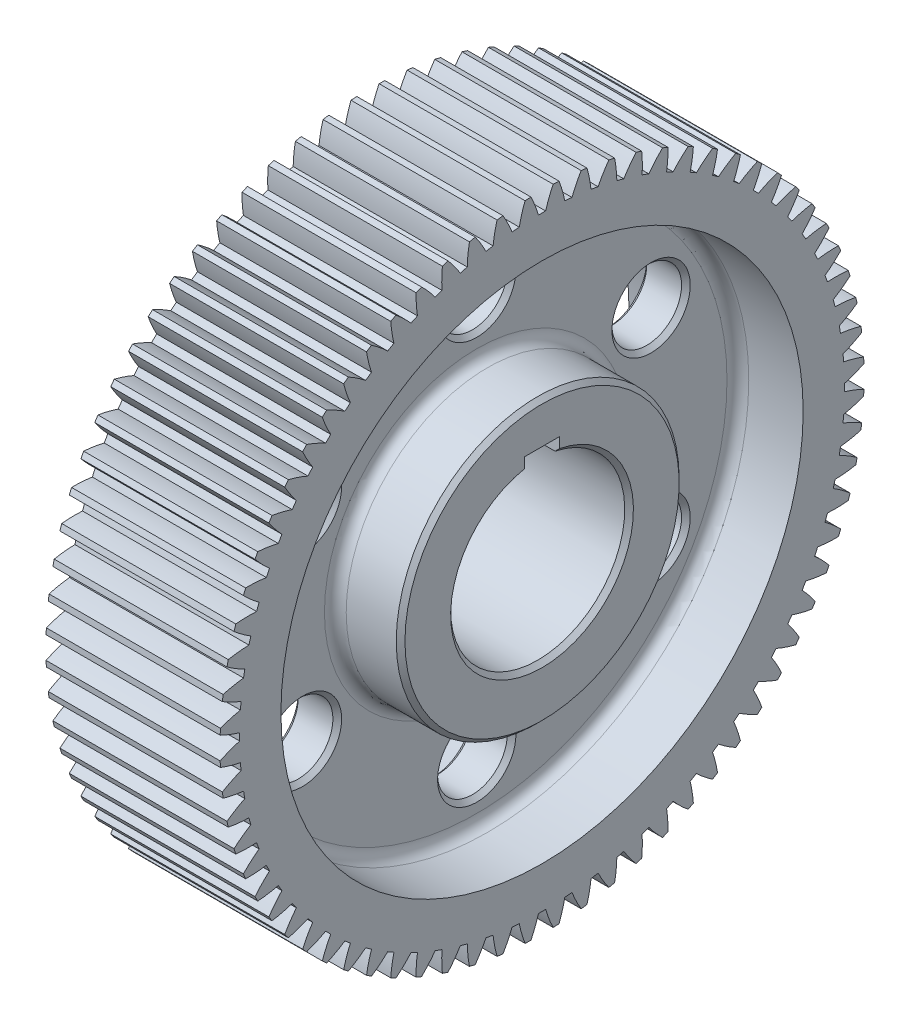
SolidWorks part; units mm, degrees
material "Plain Carbon Steel"
ref_plane "Plane1" through (0, 0, 0) normal (0, 0, 1) x (1, 0, 0)
ref_plane "Plane2" through (0, 0, 0) normal (0, 1, 0) x (1, 0, 0)
ref_plane "Plane3" through (0, 0, 0) normal (1, 0, 0) x (0, 0, -1)
sketch "HoldingSke" plane through (0, 0, 0) normal (0, 1, 0) x (1, 0, 0)
  line L0 (0, 0) -> (0.0773, -0.2378)
  line L1 (-15, 0) -> (100, 0) construction
  line L2 (0, 0) -> (-2.1039, 2.3779)
  line L3 (0, 0) -> (-11.863, 4.5341)
  line L4 (0, 0) -> (2.6687, 8.2133)
  line L5 (0, 0) -> (-46.8476, -17.4728)
  line L6 (0, 0) -> (-66.317, -44.7443)
  line L7 (-2.1039, 2.3779) -> (15.1161, 80.5027)
  line L8 (-76.2, 54.61) -> (-70.8, 54.61)
  line L9 (-71.009, 38.7566) -> (-53.1078, 45.2721)
  line L10 (-76.2, 71.12) -> (104.1128, 71.12)
  line L11 (0, 0) -> (-80, 0)
  line L12 (-76.2, 101.6) -> (-76.073, 101.6)
  line L13 (24.9733, 27.94) -> (52.9518, 28.4284)
  line L14 (24.9733, 27.94) -> (24.9743, 27.94)
  line L15 (24.9733, 27.94) -> (100.4006, 29.5858)
  line L16 (-63.627, -4) -> (-12.827, -4)
  circle A0 centre (0, 0) radius 40
  circle A1 centre (0, 0) radius 37.5
  circle A2 centre (0, 0) radius 37.5
  circle A3 centre (0, 0) radius 40
  dimension "Num_teeth" = 72
  dimension "Pitch_radius" = 180.3128
  dimension "Width" = 80
  dimension "Thickness" = 80
sketch "BasProSke" plane through (0, 0, 0) normal (0, 1, 0) x (1, 0, 0)
  line L0 (-10, 0) -> (60, 0) construction
  line L1 (0, 0) -> (0, 148)
  line L2 (0, 0) -> (80, 0)
  line L3 (80, 0) -> (80, 148)
  line L4 (80, 148) -> (0, 148)
  dimension "Thickness" = 80
  dimension "Diameter" = 296
revolve "Base-Revolve" add sketch "BasProSke" angle 360 about L0
sketch "TooCutSke" plane through (0, 0, 0) normal (1, 0, 0) x (0, 0, -1)
  line L1 (0, 0) -> (0, 107) construction
  line L2 (0, 0) -> (-3.3636, 143.9607) construction
  line L3 (0, 0) -> (-12.5598, 287.6668) construction
  line L4 (-3.3636, 143.9607) -> (-6.2799, 143.8334) construction
  arc A0 (1.6538, 138.9892) -> (-1.6538, 138.9892) centre (0, 0) ccw
  arc A1 (5.1137, 147.937) -> (-5.1137, 147.937) centre (0, 0) ccw
  circle A2 centre (0, 0) radius 144 construction
  circle A3 centre (0, 0) radius 135.3157 construction
  arc A4 (-1.6538, 138.9892) -> (-5.1137, 147.937) centre (-56.9206, 122.7615) ccw
  arc A5 (5.1137, 147.937) -> (1.6538, 138.9892) centre (56.9206, 122.7615) ccw
extrude "ToothCut" cut sketch "TooCutSke" along normal through all
fillet "Breaks" [suppressed] radius 0.08 tangent propagation no
fillet "RootFillets" [suppressed] radius 1.001
pattern_circular "TeethCuts" count 72 every 5 about axis through (-10, 0, 0) along (1, 0, 0) of "ToothCut", "RootFillets", "Breaks"
sketch "HubNeaOneSke" plane through (0, 0, 0) normal (-1, 0, 0) x (0, 0, 1)
  circle A0 centre (0, 0) radius 37.5
  dimension "Diameter" = 75
extrude "HubNearOne" [suppressed] add sketch "HubNeaOneSke" along normal blind 38.0001
sketch "HubNeaBotSke" plane through (0, 0, 0) normal (-1, 0, 0) x (0, 0, 1)
  circle A0 centre (0, 0) radius 37.5
  dimension "Diameter" = 75
extrude "HubNearBoth" [suppressed] add sketch "HubNeaBotSke" along normal blind 19
ref_plane "FarPln" through (80, 0, 0) normal (1, 0, 0) x (0, 0, -1)
sketch "HubFarSke" plane through (80, 0, 0) normal (1, 0, 0) x (0, 0, -1)
  circle A0 centre (0, 0) radius 37.5
  dimension "Diameter" = 75
extrude "HubFar" [suppressed] add sketch "HubFarSke" along normal blind 19
sketch "BorSke" plane through (0, 0, 0) normal (1, 0, 0) x (0, 0, -1)
  circle A0 centre (0, 0) radius 40
  dimension "Diameter" = 80
extrude "Bore" cut sketch "BorSke" along normal mid plane 160.0001
sketch "KeySke" plane through (0, 0, 0) normal (1, 0, 0) x (0, 0, -1)
  line L0 (-11, 0) -> (-11, 45.4)
  line L1 (-11, 45.4) -> (11, 45.4)
  line L2 (11, 45.4) -> (11, 0)
  line L3 (0, 0) -> (0, 34) construction
  line L4 (-11, 0) -> (11, 0)
  dimension "Width" = 22
extrude "Keyway" [suppressed] cut sketch "KeySke" along normal mid plane 160.0001
pattern_circular "Keyway2" [suppressed] count 2 every 90 about axis through (-10, 0, 0) along (1, 0, 0)
sketch "Sketch1" plane through (80, 0, 0) normal (1, 0, 0) x (0, 0, -1)
  circle A0 centre (0, 0) radius 120
  circle A1 centre (0, 0) radius 65
  dimension "D1" = 240
  dimension "D2" = 130
extrude "Cut-Extrude1" cut sketch "Sketch1" against normal blind 30
sketch "Sketch2" plane through (0, 0, 0) normal (-1, 0, 0) x (0, 0, 1)
  circle A0 centre (0, 0) radius 120
  circle A1 centre (0, 0) radius 65
  arc A288 (138.9892, 1.6538) -> (147.912, 5.1016) centre (122.7615, 56.9206) ccw
  arc A289 (147.912, 5.1016) -> (147.7938, 7.8092) centre (0, 0) ccw
  arc A290 (147.7938, 7.8092) -> (138.6044, 10.4662) centre (127.2553, -46.0046) ccw
  arc A291 (138.6044, 10.4662) -> (138.3161, 13.7612) centre (0, 0) ccw
  arc A292 (138.3161, 13.7612) -> (146.9046, 17.9736) centre (117.3334, 67.4034) ccw
  arc A293 (146.9046, 17.9736) -> (146.5508, 20.6606) centre (0, 0) ccw
  arc A294 (146.5508, 20.6606) -> (137.1648, 22.5066) centre (130.7807, -34.7385) ccw
  arc A295 (137.1648, 22.5066) -> (136.5904, 25.7639) centre (0, 0) ccw
  arc A296 (136.5904, 25.7639) -> (144.7791, 30.7087) centre (111.0123, 77.3732) ccw
  arc A297 (144.7791, 30.7087) -> (144.1925, 33.3547) centre (0, 0) ccw
  arc A298 (144.1925, 33.3547) -> (134.6812, 34.3756) centre (133.3107, -23.2081) ccw
  arc A299 (134.6812, 34.3756) -> (133.8252, 37.5705) centre (0, 0) ccw
  arc A300 (133.8252, 37.5705) -> (141.5517, 43.2102) centre (103.8464, 86.7541) ccw
  arc A301 (141.5517, 43.2102) -> (140.7367, 45.795) centre (0, 0) ccw
  arc A302 (140.7367, 45.795) -> (131.1727, 45.9831) centre (134.8261, -11.501) ccw
  arc A303 (131.1727, 45.9831) -> (130.0415, 49.0911) centre (0, 0) ccw
  arc A304 (130.0415, 49.0911) -> (137.247, 55.3828) centre (95.8901, 95.4748) ccw
  arc A305 (137.247, 55.3828) -> (136.2099, 57.8867) centre (0, 0) ccw
  arc A306 (136.2099, 57.8867) -> (126.6659, 57.2405) centre (135.3154, 0.2937) ccw
  arc A307 (126.6659, 57.2405) -> (125.268, 60.2382) centre (0, 0) ccw
  arc A308 (125.268, 60.2382) -> (131.8978, 67.1339) centre (87.204, 103.4689) ccw
  arc A309 (131.8978, 67.1339) -> (130.6464, 69.5379) centre (0, 0) ccw
  arc A310 (130.6464, 69.5379) -> (121.195, 68.0624) centre (134.7749, 12.0861) ccw
  arc A311 (121.195, 68.0624) -> (119.5413, 70.9268) centre (0, 0) ccw
  arc A312 (119.5413, 70.9268) -> (125.5448, 78.3741) centre (77.8543, 110.6755) ccw
  arc A313 (125.5448, 78.3741) -> (124.0886, 80.6599) centre (0, 0) ccw
  arc A314 (124.0886, 80.6599) -> (114.8018, 78.3662) centre (133.2087, 23.7865) ccw
  arc A315 (114.8018, 78.3662) -> (112.9047, 81.0756) centre (0, 0) ccw
  arc A316 (112.9047, 81.0756) -> (118.2363, 89.0178) centre (67.912, 117.0398) ccw
  arc A317 (118.2363, 89.0178) -> (116.5864, 91.168) centre (0, 0) ccw
  arc A318 (116.5864, 91.168) -> (107.5349, 88.0737) centre (130.6286, 35.3059) ccw
  arc A319 (107.5349, 88.0737) -> (105.4089, 90.6074) centre (0, 0) ccw
  arc A320 (105.4089, 90.6074) -> (110.028, 98.9841) centre (57.4529, 122.5133) ccw
  arc A321 (110.028, 98.9841) -> (108.197, 100.9822) centre (0, 0) ccw
  arc A322 (108.197, 100.9822) -> (99.4496, 97.1108) centre (127.0545, 46.5566) ccw
  arc A323 (99.4496, 97.1108) -> (97.1108, 99.4496) centre (0, 0) ccw
  arc A324 (97.1108, 99.4496) -> (100.9822, 108.197) centre (46.5566, 127.0545) ccw
  arc A325 (100.9822, 108.197) -> (98.9841, 110.028) centre (0, 0) ccw
  arc A326 (98.9841, 110.028) -> (90.6074, 105.4089) centre (122.5133, 57.4529) ccw
  arc A327 (90.6074, 105.4089) -> (88.0737, 107.5349) centre (0, 0) ccw
  arc A328 (88.0737, 107.5349) -> (91.168, 116.5864) centre (35.3059, 130.6286) ccw
  arc A329 (91.168, 116.5864) -> (89.0178, 118.2363) centre (0, 0) ccw
  arc A330 (89.0178, 118.2363) -> (81.0756, 112.9047) centre (117.0398, 67.912) ccw
  arc A331 (81.0756, 112.9047) -> (78.3662, 114.8018) centre (0, 0) ccw
  arc A332 (78.3662, 114.8018) -> (80.6599, 124.0886) centre (23.7865, 133.2087) ccw
  arc A333 (80.6599, 124.0886) -> (78.3741, 125.5448) centre (0, 0) ccw
  arc A334 (78.3741, 125.5448) -> (70.9268, 119.5413) centre (110.6755, 77.8543) ccw
  arc A335 (70.9268, 119.5413) -> (68.0624, 121.195) centre (0, 0) ccw
  arc A336 (68.0624, 121.195) -> (69.5379, 130.6464) centre (12.0861, 134.7749) ccw
  arc A337 (69.5379, 130.6464) -> (67.1339, 131.8978) centre (0, 0) ccw
  arc A338 (67.1339, 131.8978) -> (60.2382, 125.268) centre (103.4689, 87.204) ccw
  arc A339 (60.2382, 125.268) -> (57.2405, 126.6659) centre (0, 0) ccw
  arc A340 (57.2405, 126.6659) -> (57.8867, 136.2099) centre (0.2937, 135.3154) ccw
  arc A341 (57.8867, 136.2099) -> (55.3828, 137.247) centre (0, 0) ccw
  arc A342 (55.3828, 137.247) -> (49.0911, 130.0415) centre (95.4748, 95.8901) ccw
  arc A343 (49.0911, 130.0415) -> (45.9831, 131.1727) centre (0, 0) ccw
  arc A344 (45.9831, 131.1727) -> (45.795, 140.7367) centre (-11.501, 134.8261) ccw
  arc A345 (45.795, 140.7367) -> (43.2102, 141.5517) centre (0, 0) ccw
  arc A346 (43.2102, 141.5517) -> (37.5705, 133.8252) centre (86.7541, 103.8464) ccw
  arc A347 (37.5705, 133.8252) -> (34.3756, 134.6812) centre (0, 0) ccw
  arc A348 (34.3756, 134.6812) -> (33.3547, 144.1925) centre (-23.2081, 133.3107) ccw
  arc A349 (33.3547, 144.1925) -> (30.7087, 144.7791) centre (0, 0) ccw
  arc A350 (30.7087, 144.7791) -> (25.7639, 136.5904) centre (77.3732, 111.0123) ccw
  arc A351 (25.7639, 136.5904) -> (22.5066, 137.1648) centre (0, 0) ccw
  arc A352 (22.5066, 137.1648) -> (20.6606, 146.5508) centre (-34.7385, 130.7807) ccw
  arc A353 (20.6606, 146.5508) -> (17.9736, 146.9046) centre (0, 0) ccw
  arc A354 (17.9736, 146.9046) -> (13.7612, 138.3161) centre (67.4034, 117.3334) ccw
  arc A355 (13.7612, 138.3161) -> (10.4662, 138.6044) centre (0, 0) ccw
  arc A356 (10.4662, 138.6044) -> (7.8092, 147.7938) centre (-46.0046, 127.2553) ccw
  arc A357 (7.8092, 147.7938) -> (5.1016, 147.912) centre (0, 0) ccw
  arc A358 (5.1016, 147.912) -> (1.6538, 138.9892) centre (56.9206, 122.7615) ccw
  arc A359 (1.6538, 138.9892) -> (-1.6538, 138.9892) centre (0, 0) ccw
  arc A360 (-1.6538, 138.9892) -> (-5.1016, 147.912) centre (-56.9206, 122.7615) ccw
  arc A361 (-5.1016, 147.912) -> (-7.8092, 147.7938) centre (0, 0) ccw
  arc A362 (-7.8092, 147.7938) -> (-10.4662, 138.6044) centre (46.0046, 127.2553) ccw
  arc A363 (-10.4662, 138.6044) -> (-13.7612, 138.3161) centre (0, 0) ccw
  arc A364 (-13.7612, 138.3161) -> (-17.9736, 146.9046) centre (-67.4034, 117.3334) ccw
  arc A365 (-17.9736, 146.9046) -> (-20.6606, 146.5508) centre (0, 0) ccw
  arc A366 (-20.6606, 146.5508) -> (-22.5066, 137.1648) centre (34.7385, 130.7807) ccw
  arc A367 (-22.5066, 137.1648) -> (-25.7639, 136.5904) centre (0, 0) ccw
  arc A368 (-25.7639, 136.5904) -> (-30.7087, 144.7791) centre (-77.3732, 111.0123) ccw
  arc A369 (-30.7087, 144.7791) -> (-33.3547, 144.1925) centre (0, 0) ccw
  arc A370 (-33.3547, 144.1925) -> (-34.3756, 134.6812) centre (23.2081, 133.3107) ccw
  arc A371 (-34.3756, 134.6812) -> (-37.5705, 133.8252) centre (0, 0) ccw
  arc A372 (-37.5705, 133.8252) -> (-43.2102, 141.5517) centre (-86.7541, 103.8464) ccw
  arc A373 (-43.2102, 141.5517) -> (-45.795, 140.7367) centre (0, 0) ccw
  arc A374 (-45.795, 140.7367) -> (-45.9831, 131.1727) centre (11.501, 134.8261) ccw
  arc A375 (-45.9831, 131.1727) -> (-49.0911, 130.0415) centre (0, 0) ccw
  arc A376 (-49.0911, 130.0415) -> (-55.3828, 137.247) centre (-95.4748, 95.8901) ccw
  arc A377 (-55.3828, 137.247) -> (-57.8867, 136.2099) centre (0, 0) ccw
  arc A378 (-57.8867, 136.2099) -> (-57.2405, 126.6659) centre (-0.2937, 135.3154) ccw
  arc A379 (-57.2405, 126.6659) -> (-60.2382, 125.268) centre (0, 0) ccw
  arc A380 (-60.2382, 125.268) -> (-67.1339, 131.8978) centre (-103.4689, 87.204) ccw
  arc A381 (-67.1339, 131.8978) -> (-69.5379, 130.6464) centre (0, 0) ccw
  arc A382 (-69.5379, 130.6464) -> (-68.0624, 121.195) centre (-12.0861, 134.7749) ccw
  arc A383 (-68.0624, 121.195) -> (-70.9268, 119.5413) centre (0, 0) ccw
  arc A384 (-70.9268, 119.5413) -> (-78.3741, 125.5448) centre (-110.6755, 77.8543) ccw
  arc A385 (-78.3741, 125.5448) -> (-80.6599, 124.0886) centre (0, 0) ccw
  arc A386 (-80.6599, 124.0886) -> (-78.3662, 114.8018) centre (-23.7865, 133.2087) ccw
  arc A387 (-78.3662, 114.8018) -> (-81.0756, 112.9047) centre (0, 0) ccw
  arc A388 (-81.0756, 112.9047) -> (-89.0178, 118.2363) centre (-117.0398, 67.912) ccw
  arc A389 (-89.0178, 118.2363) -> (-91.168, 116.5864) centre (0, 0) ccw
  arc A390 (-91.168, 116.5864) -> (-88.0737, 107.5349) centre (-35.3059, 130.6286) ccw
  arc A391 (-88.0737, 107.5349) -> (-90.6074, 105.4089) centre (0, 0) ccw
  arc A392 (-90.6074, 105.4089) -> (-98.9841, 110.028) centre (-122.5133, 57.4529) ccw
  arc A393 (-98.9841, 110.028) -> (-100.9822, 108.197) centre (0, 0) ccw
  arc A394 (-100.9822, 108.197) -> (-97.1108, 99.4496) centre (-46.5566, 127.0545) ccw
  arc A395 (-97.1108, 99.4496) -> (-99.4496, 97.1108) centre (0, 0) ccw
  arc A396 (-99.4496, 97.1108) -> (-108.197, 100.9822) centre (-127.0545, 46.5566) ccw
  arc A397 (-108.197, 100.9822) -> (-110.028, 98.9841) centre (0, 0) ccw
  arc A398 (-110.028, 98.9841) -> (-105.4089, 90.6074) centre (-57.4529, 122.5133) ccw
  arc A399 (-105.4089, 90.6074) -> (-107.5349, 88.0737) centre (0, 0) ccw
  arc A400 (-107.5349, 88.0737) -> (-116.5864, 91.168) centre (-130.6286, 35.3059) ccw
  arc A401 (-116.5864, 91.168) -> (-118.2363, 89.0178) centre (0, 0) ccw
  arc A402 (-118.2363, 89.0178) -> (-112.9047, 81.0756) centre (-67.912, 117.0398) ccw
  arc A403 (-112.9047, 81.0756) -> (-114.8018, 78.3662) centre (0, 0) ccw
  arc A404 (-114.8018, 78.3662) -> (-124.0886, 80.6599) centre (-133.2087, 23.7865) ccw
  arc A405 (-124.0886, 80.6599) -> (-125.5448, 78.3741) centre (0, 0) ccw
  arc A406 (-125.5448, 78.3741) -> (-119.5413, 70.9268) centre (-77.8543, 110.6755) ccw
  arc A407 (-119.5413, 70.9268) -> (-121.195, 68.0624) centre (0, 0) ccw
  arc A408 (-121.195, 68.0624) -> (-130.6464, 69.5379) centre (-134.7749, 12.0861) ccw
  arc A409 (-130.6464, 69.5379) -> (-131.8978, 67.1339) centre (0, 0) ccw
  arc A410 (-131.8978, 67.1339) -> (-125.268, 60.2382) centre (-87.204, 103.4689) ccw
  arc A411 (-125.268, 60.2382) -> (-126.6659, 57.2405) centre (0, 0) ccw
  arc A412 (-126.6659, 57.2405) -> (-136.2099, 57.8867) centre (-135.3154, 0.2937) ccw
  arc A413 (-136.2099, 57.8867) -> (-137.247, 55.3828) centre (0, 0) ccw
  arc A414 (-137.247, 55.3828) -> (-130.0415, 49.0911) centre (-95.8901, 95.4748) ccw
  arc A415 (-130.0415, 49.0911) -> (-131.1727, 45.9831) centre (0, 0) ccw
  arc A416 (-131.1727, 45.9831) -> (-140.7367, 45.795) centre (-134.8261, -11.501) ccw
  arc A417 (-140.7367, 45.795) -> (-141.5517, 43.2102) centre (0, 0) ccw
  arc A418 (-141.5517, 43.2102) -> (-133.8252, 37.5705) centre (-103.8464, 86.7541) ccw
  arc A419 (-133.8252, 37.5705) -> (-134.6812, 34.3756) centre (0, 0) ccw
  arc A420 (-134.6812, 34.3756) -> (-144.1925, 33.3547) centre (-133.3107, -23.2081) ccw
  arc A421 (-144.1925, 33.3547) -> (-144.7791, 30.7087) centre (0, 0) ccw
  arc A422 (-144.7791, 30.7087) -> (-136.5904, 25.7639) centre (-111.0123, 77.3732) ccw
  arc A423 (-136.5904, 25.7639) -> (-137.1648, 22.5066) centre (0, 0) ccw
  arc A424 (-137.1648, 22.5066) -> (-146.5508, 20.6606) centre (-130.7807, -34.7385) ccw
  arc A425 (-146.5508, 20.6606) -> (-146.9046, 17.9736) centre (0, 0) ccw
  arc A426 (-146.9046, 17.9736) -> (-138.3161, 13.7612) centre (-117.3334, 67.4034) ccw
  arc A427 (-138.3161, 13.7612) -> (-138.6044, 10.4662) centre (0, 0) ccw
  arc A428 (-138.6044, 10.4662) -> (-147.7938, 7.8092) centre (-127.2553, -46.0046) ccw
  arc A429 (-147.7938, 7.8092) -> (-147.912, 5.1016) centre (0, 0) ccw
  arc A430 (-147.912, 5.1016) -> (-138.9892, 1.6538) centre (-122.7615, 56.9206) ccw
  arc A431 (-138.9892, 1.6538) -> (-138.9892, -1.6538) centre (0, 0) ccw
  arc A432 (-138.9892, -1.6538) -> (-147.912, -5.1016) centre (-122.7615, -56.9206) ccw
  arc A433 (-147.912, -5.1016) -> (-147.7938, -7.8092) centre (0, 0) ccw
  arc A434 (-147.7938, -7.8092) -> (-138.6044, -10.4662) centre (-127.2553, 46.0046) ccw
  arc A435 (-138.6044, -10.4662) -> (-138.3161, -13.7612) centre (0, 0) ccw
  arc A436 (-138.3161, -13.7612) -> (-146.9046, -17.9736) centre (-117.3334, -67.4034) ccw
  arc A437 (-146.9046, -17.9736) -> (-146.5508, -20.6606) centre (0, 0) ccw
  arc A438 (-146.5508, -20.6606) -> (-137.1648, -22.5066) centre (-130.7807, 34.7385) ccw
  arc A439 (-137.1648, -22.5066) -> (-136.5904, -25.7639) centre (0, 0) ccw
  arc A440 (-136.5904, -25.7639) -> (-144.7791, -30.7087) centre (-111.0123, -77.3732) ccw
  arc A441 (-144.7791, -30.7087) -> (-144.1925, -33.3547) centre (0, 0) ccw
  arc A442 (-144.1925, -33.3547) -> (-134.6812, -34.3756) centre (-133.3107, 23.2081) ccw
  arc A443 (-134.6812, -34.3756) -> (-133.8252, -37.5705) centre (0, 0) ccw
  arc A444 (-133.8252, -37.5705) -> (-141.5517, -43.2102) centre (-103.8464, -86.7541) ccw
  arc A445 (-141.5517, -43.2102) -> (-140.7367, -45.795) centre (0, 0) ccw
  arc A446 (-140.7367, -45.795) -> (-131.1727, -45.9831) centre (-134.8261, 11.501) ccw
  arc A447 (-131.1727, -45.9831) -> (-130.0415, -49.0911) centre (0, 0) ccw
  arc A448 (-130.0415, -49.0911) -> (-137.247, -55.3828) centre (-95.8901, -95.4748) ccw
  arc A449 (-137.247, -55.3828) -> (-136.2099, -57.8867) centre (0, 0) ccw
  arc A450 (-136.2099, -57.8867) -> (-126.6659, -57.2405) centre (-135.3154, -0.2937) ccw
  arc A451 (-126.6659, -57.2405) -> (-125.268, -60.2382) centre (0, 0) ccw
  arc A452 (-125.268, -60.2382) -> (-131.8978, -67.1339) centre (-87.204, -103.4689) ccw
  arc A453 (-131.8978, -67.1339) -> (-130.6464, -69.5379) centre (0, 0) ccw
  arc A454 (-130.6464, -69.5379) -> (-121.195, -68.0624) centre (-134.7749, -12.0861) ccw
  arc A455 (-121.195, -68.0624) -> (-119.5413, -70.9268) centre (0, 0) ccw
  arc A456 (-119.5413, -70.9268) -> (-125.5448, -78.3741) centre (-77.8543, -110.6755) ccw
  arc A457 (-125.5448, -78.3741) -> (-124.0886, -80.6599) centre (0, 0) ccw
  arc A458 (-124.0886, -80.6599) -> (-114.8018, -78.3662) centre (-133.2087, -23.7865) ccw
  arc A459 (-114.8018, -78.3662) -> (-112.9047, -81.0756) centre (0, 0) ccw
  arc A460 (-112.9047, -81.0756) -> (-118.2363, -89.0178) centre (-67.912, -117.0398) ccw
  arc A461 (-118.2363, -89.0178) -> (-116.5864, -91.168) centre (0, 0) ccw
  arc A462 (-116.5864, -91.168) -> (-107.5349, -88.0737) centre (-130.6286, -35.3059) ccw
  arc A463 (-107.5349, -88.0737) -> (-105.4089, -90.6074) centre (0, 0) ccw
  arc A464 (-105.4089, -90.6074) -> (-110.028, -98.9841) centre (-57.4529, -122.5133) ccw
  arc A465 (-110.028, -98.9841) -> (-108.197, -100.9822) centre (0, 0) ccw
  arc A466 (-108.197, -100.9822) -> (-99.4496, -97.1108) centre (-127.0545, -46.5566) ccw
  arc A467 (-99.4496, -97.1108) -> (-97.1108, -99.4496) centre (0, 0) ccw
  arc A468 (-97.1108, -99.4496) -> (-100.9822, -108.197) centre (-46.5566, -127.0545) ccw
  arc A469 (-100.9822, -108.197) -> (-98.9841, -110.028) centre (0, 0) ccw
  arc A470 (-98.9841, -110.028) -> (-90.6074, -105.4089) centre (-122.5133, -57.4529) ccw
  arc A471 (-90.6074, -105.4089) -> (-88.0737, -107.5349) centre (0, 0) ccw
  arc A472 (-88.0737, -107.5349) -> (-91.168, -116.5864) centre (-35.3059, -130.6286) ccw
  arc A473 (-91.168, -116.5864) -> (-89.0178, -118.2363) centre (0, 0) ccw
  arc A474 (-89.0178, -118.2363) -> (-81.0756, -112.9047) centre (-117.0398, -67.912) ccw
  arc A475 (-81.0756, -112.9047) -> (-78.3662, -114.8018) centre (0, 0) ccw
  arc A476 (-78.3662, -114.8018) -> (-80.6599, -124.0886) centre (-23.7865, -133.2087) ccw
  arc A477 (-80.6599, -124.0886) -> (-78.3741, -125.5448) centre (0, 0) ccw
  arc A478 (-78.3741, -125.5448) -> (-70.9268, -119.5413) centre (-110.6755, -77.8543) ccw
  arc A479 (-70.9268, -119.5413) -> (-68.0624, -121.195) centre (0, 0) ccw
  arc A480 (-68.0624, -121.195) -> (-69.5379, -130.6464) centre (-12.0861, -134.7749) ccw
  arc A481 (-69.5379, -130.6464) -> (-67.1339, -131.8978) centre (0, 0) ccw
  arc A482 (-67.1339, -131.8978) -> (-60.2382, -125.268) centre (-103.4689, -87.204) ccw
  arc A483 (-60.2382, -125.268) -> (-57.2405, -126.6659) centre (0, 0) ccw
  arc A484 (-57.2405, -126.6659) -> (-57.8867, -136.2099) centre (-0.2937, -135.3154) ccw
  arc A485 (-57.8867, -136.2099) -> (-55.3828, -137.247) centre (0, 0) ccw
  arc A486 (-55.3828, -137.247) -> (-49.0911, -130.0415) centre (-95.4748, -95.8901) ccw
  arc A487 (-49.0911, -130.0415) -> (-45.9831, -131.1727) centre (0, 0) ccw
  arc A488 (-45.9831, -131.1727) -> (-45.795, -140.7367) centre (11.501, -134.8261) ccw
  arc A489 (-45.795, -140.7367) -> (-43.2102, -141.5517) centre (0, 0) ccw
  arc A490 (-43.2102, -141.5517) -> (-37.5705, -133.8252) centre (-86.7541, -103.8464) ccw
  arc A491 (-37.5705, -133.8252) -> (-34.3756, -134.6812) centre (0, 0) ccw
  arc A492 (-34.3756, -134.6812) -> (-33.3547, -144.1925) centre (23.2081, -133.3107) ccw
  arc A493 (-33.3547, -144.1925) -> (-30.7087, -144.7791) centre (0, 0) ccw
  arc A494 (-30.7087, -144.7791) -> (-25.7639, -136.5904) centre (-77.3732, -111.0123) ccw
  arc A495 (-25.7639, -136.5904) -> (-22.5066, -137.1648) centre (0, 0) ccw
  arc A496 (-22.5066, -137.1648) -> (-20.6606, -146.5508) centre (34.7385, -130.7807) ccw
  arc A497 (-20.6606, -146.5508) -> (-17.9736, -146.9046) centre (0, 0) ccw
  arc A498 (-17.9736, -146.9046) -> (-13.7612, -138.3161) centre (-67.4034, -117.3334) ccw
  arc A499 (-13.7612, -138.3161) -> (-10.4662, -138.6044) centre (0, 0) ccw
  arc A500 (-10.4662, -138.6044) -> (-7.8092, -147.7938) centre (46.0046, -127.2553) ccw
  arc A501 (-7.8092, -147.7938) -> (-5.1016, -147.912) centre (0, 0) ccw
  arc A502 (-5.1016, -147.912) -> (-1.6538, -138.9892) centre (-56.9206, -122.7615) ccw
  arc A503 (-1.6538, -138.9892) -> (1.6538, -138.9892) centre (0, 0) ccw
  arc A504 (1.6538, -138.9892) -> (5.1016, -147.912) centre (56.9206, -122.7615) ccw
  arc A505 (5.1016, -147.912) -> (7.8092, -147.7938) centre (0, 0) ccw
  arc A506 (7.8092, -147.7938) -> (10.4662, -138.6044) centre (-46.0046, -127.2553) ccw
  arc A507 (10.4662, -138.6044) -> (13.7612, -138.3161) centre (0, 0) ccw
  arc A508 (13.7612, -138.3161) -> (17.9736, -146.9046) centre (67.4034, -117.3334) ccw
  arc A509 (17.9736, -146.9046) -> (20.6606, -146.5508) centre (0, 0) ccw
  arc A510 (20.6606, -146.5508) -> (22.5066, -137.1648) centre (-34.7385, -130.7807) ccw
  arc A511 (22.5066, -137.1648) -> (25.7639, -136.5904) centre (0, 0) ccw
  arc A512 (25.7639, -136.5904) -> (30.7087, -144.7791) centre (77.3732, -111.0123) ccw
  arc A513 (30.7087, -144.7791) -> (33.3547, -144.1925) centre (0, 0) ccw
  arc A514 (33.3547, -144.1925) -> (34.3756, -134.6812) centre (-23.2081, -133.3107) ccw
  arc A515 (34.3756, -134.6812) -> (37.5705, -133.8252) centre (0, 0) ccw
  arc A516 (37.5705, -133.8252) -> (43.2102, -141.5517) centre (86.7541, -103.8464) ccw
  arc A517 (43.2102, -141.5517) -> (45.795, -140.7367) centre (0, 0) ccw
  arc A518 (45.795, -140.7367) -> (45.9831, -131.1727) centre (-11.501, -134.8261) ccw
  arc A519 (45.9831, -131.1727) -> (49.0911, -130.0415) centre (0, 0) ccw
  arc A520 (49.0911, -130.0415) -> (55.3828, -137.247) centre (95.4748, -95.8901) ccw
  arc A521 (55.3828, -137.247) -> (57.8867, -136.2099) centre (0, 0) ccw
  arc A522 (57.8867, -136.2099) -> (57.2405, -126.6659) centre (0.2937, -135.3154) ccw
  arc A523 (57.2405, -126.6659) -> (60.2382, -125.268) centre (0, 0) ccw
  arc A524 (60.2382, -125.268) -> (67.1339, -131.8978) centre (103.4689, -87.204) ccw
  arc A525 (67.1339, -131.8978) -> (69.5379, -130.6464) centre (0, 0) ccw
  arc A526 (69.5379, -130.6464) -> (68.0624, -121.195) centre (12.0861, -134.7749) ccw
  arc A527 (68.0624, -121.195) -> (70.9268, -119.5413) centre (0, 0) ccw
  arc A528 (70.9268, -119.5413) -> (78.3741, -125.5448) centre (110.6755, -77.8543) ccw
  arc A529 (78.3741, -125.5448) -> (80.6599, -124.0886) centre (0, 0) ccw
  arc A530 (80.6599, -124.0886) -> (78.3662, -114.8018) centre (23.7865, -133.2087) ccw
  arc A531 (78.3662, -114.8018) -> (81.0756, -112.9047) centre (0, 0) ccw
  arc A532 (81.0756, -112.9047) -> (89.0178, -118.2363) centre (117.0398, -67.912) ccw
  arc A533 (89.0178, -118.2363) -> (91.168, -116.5864) centre (0, 0) ccw
  arc A534 (91.168, -116.5864) -> (88.0737, -107.5349) centre (35.3059, -130.6286) ccw
  arc A535 (88.0737, -107.5349) -> (90.6074, -105.4089) centre (0, 0) ccw
  arc A536 (90.6074, -105.4089) -> (98.9841, -110.028) centre (122.5133, -57.4529) ccw
  arc A537 (98.9841, -110.028) -> (100.9822, -108.197) centre (0, 0) ccw
  arc A538 (100.9822, -108.197) -> (97.1108, -99.4496) centre (46.5566, -127.0545) ccw
  arc A539 (97.1108, -99.4496) -> (99.4496, -97.1108) centre (0, 0) ccw
  arc A540 (99.4496, -97.1108) -> (108.197, -100.9822) centre (127.0545, -46.5566) ccw
  arc A541 (108.197, -100.9822) -> (110.028, -98.9841) centre (0, 0) ccw
  arc A542 (110.028, -98.9841) -> (105.4089, -90.6074) centre (57.4529, -122.5133) ccw
  arc A543 (105.4089, -90.6074) -> (107.5349, -88.0737) centre (0, 0) ccw
  arc A544 (107.5349, -88.0737) -> (116.5864, -91.168) centre (130.6286, -35.3059) ccw
  arc A545 (116.5864, -91.168) -> (118.2363, -89.0178) centre (0, 0) ccw
  arc A546 (118.2363, -89.0178) -> (112.9047, -81.0756) centre (67.912, -117.0398) ccw
  arc A547 (112.9047, -81.0756) -> (114.8018, -78.3662) centre (0, 0) ccw
  arc A548 (114.8018, -78.3662) -> (124.0886, -80.6599) centre (133.2087, -23.7865) ccw
  arc A549 (124.0886, -80.6599) -> (125.5448, -78.3741) centre (0, 0) ccw
  arc A550 (125.5448, -78.3741) -> (119.5413, -70.9268) centre (77.8543, -110.6755) ccw
  arc A551 (119.5413, -70.9268) -> (121.195, -68.0624) centre (0, 0) ccw
  arc A552 (121.195, -68.0624) -> (130.6464, -69.5379) centre (134.7749, -12.0861) ccw
  arc A553 (130.6464, -69.5379) -> (131.8978, -67.1339) centre (0, 0) ccw
  arc A554 (131.8978, -67.1339) -> (125.268, -60.2382) centre (87.204, -103.4689) ccw
  arc A555 (125.268, -60.2382) -> (126.6659, -57.2405) centre (0, 0) ccw
  arc A556 (126.6659, -57.2405) -> (136.2099, -57.8867) centre (135.3154, -0.2937) ccw
  arc A557 (136.2099, -57.8867) -> (137.247, -55.3828) centre (0, 0) ccw
  arc A558 (137.247, -55.3828) -> (130.0415, -49.0911) centre (95.8901, -95.4748) ccw
  arc A559 (130.0415, -49.0911) -> (131.1727, -45.9831) centre (0, 0) ccw
  arc A560 (131.1727, -45.9831) -> (140.7367, -45.795) centre (134.8261, 11.501) ccw
  arc A561 (140.7367, -45.795) -> (141.5517, -43.2102) centre (0, 0) ccw
  arc A562 (141.5517, -43.2102) -> (133.8252, -37.5705) centre (103.8464, -86.7541) ccw
  arc A563 (133.8252, -37.5705) -> (134.6812, -34.3756) centre (0, 0) ccw
  arc A564 (134.6812, -34.3756) -> (144.1925, -33.3547) centre (133.3107, 23.2081) ccw
  arc A565 (144.1925, -33.3547) -> (144.7791, -30.7087) centre (0, 0) ccw
  arc A566 (144.7791, -30.7087) -> (136.5904, -25.7639) centre (111.0123, -77.3732) ccw
  arc A567 (136.5904, -25.7639) -> (137.1648, -22.5066) centre (0, 0) ccw
  arc A568 (137.1648, -22.5066) -> (146.5508, -20.6606) centre (130.7807, 34.7385) ccw
  arc A569 (146.5508, -20.6606) -> (146.9046, -17.9736) centre (0, 0) ccw
  arc A570 (146.9046, -17.9736) -> (138.3161, -13.7612) centre (117.3334, -67.4034) ccw
  arc A571 (138.3161, -13.7612) -> (138.6044, -10.4662) centre (0, 0) ccw
  arc A572 (138.6044, -10.4662) -> (147.7938, -7.8092) centre (127.2553, 46.0046) ccw
  arc A573 (147.7938, -7.8092) -> (147.912, -5.1016) centre (0, 0) ccw
  arc A574 (147.912, -5.1016) -> (138.9892, -1.6538) centre (122.7615, -56.9206) ccw
  arc A575 (138.9892, -1.6538) -> (138.9892, 1.6538) centre (0, 0) ccw
  arc A576 (138.9892, 1.6538) -> (147.912, 5.1016) centre (122.7615, 56.9206) ccw
  arc A577 (147.912, 5.1016) -> (147.7938, 7.8092) centre (0, 0) ccw
  arc A578 (147.7938, 7.8092) -> (138.6044, 10.4662) centre (127.2553, -46.0046) ccw
  arc A579 (138.6044, 10.4662) -> (138.3161, 13.7612) centre (0, 0) ccw
  arc A580 (138.3161, 13.7612) -> (146.9046, 17.9736) centre (117.3334, 67.4034) ccw
  arc A581 (146.9046, 17.9736) -> (146.5508, 20.6606) centre (0, 0) ccw
  arc A582 (146.5508, 20.6606) -> (137.1648, 22.5066) centre (130.7807, -34.7385) ccw
  arc A583 (137.1648, 22.5066) -> (136.5904, 25.7639) centre (0, 0) ccw
  arc A584 (136.5904, 25.7639) -> (144.7791, 30.7087) centre (111.0123, 77.3732) ccw
  arc A585 (144.7791, 30.7087) -> (144.1925, 33.3547) centre (0, 0) ccw
  arc A586 (144.1925, 33.3547) -> (134.6812, 34.3756) centre (133.3107, -23.2081) ccw
  arc A587 (134.6812, 34.3756) -> (133.8252, 37.5705) centre (0, 0) ccw
  arc A588 (133.8252, 37.5705) -> (141.5517, 43.2102) centre (103.8464, 86.7541) ccw
  arc A589 (141.5517, 43.2102) -> (140.7367, 45.795) centre (0, 0) ccw
  arc A590 (140.7367, 45.795) -> (131.1727, 45.9831) centre (134.8261, -11.501) ccw
  arc A591 (131.1727, 45.9831) -> (130.0415, 49.0911) centre (0, 0) ccw
  arc A592 (130.0415, 49.0911) -> (137.247, 55.3828) centre (95.8901, 95.4748) ccw
  arc A593 (137.247, 55.3828) -> (136.2099, 57.8867) centre (0, 0) ccw
  arc A594 (136.2099, 57.8867) -> (126.6659, 57.2405) centre (135.3154, 0.2937) ccw
  arc A595 (126.6659, 57.2405) -> (125.268, 60.2382) centre (0, 0) ccw
  arc A596 (125.268, 60.2382) -> (131.8978, 67.1339) centre (87.204, 103.4689) ccw
  arc A597 (131.8978, 67.1339) -> (130.6464, 69.5379) centre (0, 0) ccw
  arc A598 (130.6464, 69.5379) -> (121.195, 68.0624) centre (134.7749, 12.0861) ccw
  arc A599 (121.195, 68.0624) -> (119.5413, 70.9268) centre (0, 0) ccw
  arc A600 (119.5413, 70.9268) -> (125.5448, 78.3741) centre (77.8543, 110.6755) ccw
  arc A601 (125.5448, 78.3741) -> (124.0886, 80.6599) centre (0, 0) ccw
  arc A602 (124.0886, 80.6599) -> (114.8018, 78.3662) centre (133.2087, 23.7865) ccw
  arc A603 (114.8018, 78.3662) -> (112.9047, 81.0756) centre (0, 0) ccw
  arc A604 (112.9047, 81.0756) -> (118.2363, 89.0178) centre (67.912, 117.0398) ccw
  arc A605 (118.2363, 89.0178) -> (116.5864, 91.168) centre (0, 0) ccw
  arc A606 (116.5864, 91.168) -> (107.5349, 88.0737) centre (130.6286, 35.3059) ccw
  arc A607 (107.5349, 88.0737) -> (105.4089, 90.6074) centre (0, 0) ccw
  arc A608 (105.4089, 90.6074) -> (110.028, 98.9841) centre (57.4529, 122.5133) ccw
  arc A609 (110.028, 98.9841) -> (108.197, 100.9822) centre (0, 0) ccw
  arc A610 (108.197, 100.9822) -> (99.4496, 97.1108) centre (127.0545, 46.5566) ccw
  arc A611 (99.4496, 97.1108) -> (97.1108, 99.4496) centre (0, 0) ccw
  arc A612 (97.1108, 99.4496) -> (100.9822, 108.197) centre (46.5566, 127.0545) ccw
  arc A613 (100.9822, 108.197) -> (98.9841, 110.028) centre (0, 0) ccw
  arc A614 (98.9841, 110.028) -> (90.6074, 105.4089) centre (122.5133, 57.4529) ccw
  arc A615 (90.6074, 105.4089) -> (88.0737, 107.5349) centre (0, 0) ccw
  arc A616 (88.0737, 107.5349) -> (91.168, 116.5864) centre (35.3059, 130.6286) ccw
  arc A617 (91.168, 116.5864) -> (89.0178, 118.2363) centre (0, 0) ccw
  arc A618 (89.0178, 118.2363) -> (81.0756, 112.9047) centre (117.0398, 67.912) ccw
  arc A619 (81.0756, 112.9047) -> (78.3662, 114.8018) centre (0, 0) ccw
  arc A620 (78.3662, 114.8018) -> (80.6599, 124.0886) centre (23.7865, 133.2087) ccw
  arc A621 (80.6599, 124.0886) -> (78.3741, 125.5448) centre (0, 0) ccw
  arc A622 (78.3741, 125.5448) -> (70.9268, 119.5413) centre (110.6755, 77.8543) ccw
  arc A623 (70.9268, 119.5413) -> (68.0624, 121.195) centre (0, 0) ccw
  arc A624 (68.0624, 121.195) -> (69.5379, 130.6464) centre (12.0861, 134.7749) ccw
  arc A625 (69.5379, 130.6464) -> (67.1339, 131.8978) centre (0, 0) ccw
  arc A626 (67.1339, 131.8978) -> (60.2382, 125.268) centre (103.4689, 87.204) ccw
  arc A627 (60.2382, 125.268) -> (57.2405, 126.6659) centre (0, 0) ccw
  arc A628 (57.2405, 126.6659) -> (57.8867, 136.2099) centre (0.2937, 135.3154) ccw
  arc A629 (57.8867, 136.2099) -> (55.3828, 137.247) centre (0, 0) ccw
  arc A630 (55.3828, 137.247) -> (49.0911, 130.0415) centre (95.4748, 95.8901) ccw
  arc A631 (49.0911, 130.0415) -> (45.9831, 131.1727) centre (0, 0) ccw
  arc A632 (45.9831, 131.1727) -> (45.795, 140.7367) centre (-11.501, 134.8261) ccw
  arc A633 (45.795, 140.7367) -> (43.2102, 141.5517) centre (0, 0) ccw
  arc A634 (43.2102, 141.5517) -> (37.5705, 133.8252) centre (86.7541, 103.8464) ccw
  arc A635 (37.5705, 133.8252) -> (34.3756, 134.6812) centre (0, 0) ccw
  arc A636 (34.3756, 134.6812) -> (33.3547, 144.1925) centre (-23.2081, 133.3107) ccw
  arc A637 (33.3547, 144.1925) -> (30.7087, 144.7791) centre (0, 0) ccw
  arc A638 (30.7087, 144.7791) -> (25.7639, 136.5904) centre (77.3732, 111.0123) ccw
  arc A639 (25.7639, 136.5904) -> (22.5066, 137.1648) centre (0, 0) ccw
  arc A640 (22.5066, 137.1648) -> (20.6606, 146.5508) centre (-34.7385, 130.7807) ccw
  arc A641 (20.6606, 146.5508) -> (17.9736, 146.9046) centre (0, 0) ccw
  arc A642 (17.9736, 146.9046) -> (13.7612, 138.3161) centre (67.4034, 117.3334) ccw
  arc A643 (13.7612, 138.3161) -> (10.4662, 138.6044) centre (0, 0) ccw
  arc A644 (10.4662, 138.6044) -> (7.8092, 147.7938) centre (-46.0046, 127.2553) ccw
  arc A645 (7.8092, 147.7938) -> (5.1016, 147.912) centre (0, 0) ccw
  arc A646 (5.1016, 147.912) -> (1.6538, 138.9892) centre (56.9206, 122.7615) ccw
  arc A647 (1.6538, 138.9892) -> (-1.6538, 138.9892) centre (0, 0) ccw
  arc A648 (-1.6538, 138.9892) -> (-5.1016, 147.912) centre (-56.9206, 122.7615) ccw
  arc A649 (-5.1016, 147.912) -> (-7.8092, 147.7938) centre (0, 0) ccw
  arc A650 (-7.8092, 147.7938) -> (-10.4662, 138.6044) centre (46.0046, 127.2553) ccw
  arc A651 (-10.4662, 138.6044) -> (-13.7612, 138.3161) centre (0, 0) ccw
  arc A652 (-13.7612, 138.3161) -> (-17.9736, 146.9046) centre (-67.4034, 117.3334) ccw
  arc A653 (-17.9736, 146.9046) -> (-20.6606, 146.5508) centre (0, 0) ccw
  arc A654 (-20.6606, 146.5508) -> (-22.5066, 137.1648) centre (34.7385, 130.7807) ccw
  arc A655 (-22.5066, 137.1648) -> (-25.7639, 136.5904) centre (0, 0) ccw
  arc A656 (-25.7639, 136.5904) -> (-30.7087, 144.7791) centre (-77.3732, 111.0123) ccw
  arc A657 (-30.7087, 144.7791) -> (-33.3547, 144.1925) centre (0, 0) ccw
  arc A658 (-33.3547, 144.1925) -> (-34.3756, 134.6812) centre (23.2081, 133.3107) ccw
  arc A659 (-34.3756, 134.6812) -> (-37.5705, 133.8252) centre (0, 0) ccw
  arc A660 (-37.5705, 133.8252) -> (-43.2102, 141.5517) centre (-86.7541, 103.8464) ccw
  arc A661 (-43.2102, 141.5517) -> (-45.795, 140.7367) centre (0, 0) ccw
  arc A662 (-45.795, 140.7367) -> (-45.9831, 131.1727) centre (11.501, 134.8261) ccw
  arc A663 (-45.9831, 131.1727) -> (-49.0911, 130.0415) centre (0, 0) ccw
  arc A664 (-49.0911, 130.0415) -> (-55.3828, 137.247) centre (-95.4748, 95.8901) ccw
  arc A665 (-55.3828, 137.247) -> (-57.8867, 136.2099) centre (0, 0) ccw
  arc A666 (-57.8867, 136.2099) -> (-57.2405, 126.6659) centre (-0.2937, 135.3154) ccw
  arc A667 (-57.2405, 126.6659) -> (-60.2382, 125.268) centre (0, 0) ccw
  arc A668 (-60.2382, 125.268) -> (-67.1339, 131.8978) centre (-103.4689, 87.204) ccw
  arc A669 (-67.1339, 131.8978) -> (-69.5379, 130.6464) centre (0, 0) ccw
  arc A670 (-69.5379, 130.6464) -> (-68.0624, 121.195) centre (-12.0861, 134.7749) ccw
  arc A671 (-68.0624, 121.195) -> (-70.9268, 119.5413) centre (0, 0) ccw
  arc A672 (-70.9268, 119.5413) -> (-78.3741, 125.5448) centre (-110.6755, 77.8543) ccw
  arc A673 (-78.3741, 125.5448) -> (-80.6599, 124.0886) centre (0, 0) ccw
  arc A674 (-80.6599, 124.0886) -> (-78.3662, 114.8018) centre (-23.7865, 133.2087) ccw
  arc A675 (-78.3662, 114.8018) -> (-81.0756, 112.9047) centre (0, 0) ccw
  arc A676 (-81.0756, 112.9047) -> (-89.0178, 118.2363) centre (-117.0398, 67.912) ccw
  arc A677 (-89.0178, 118.2363) -> (-91.168, 116.5864) centre (0, 0) ccw
  arc A678 (-91.168, 116.5864) -> (-88.0737, 107.5349) centre (-35.3059, 130.6286) ccw
  arc A679 (-88.0737, 107.5349) -> (-90.6074, 105.4089) centre (0, 0) ccw
  arc A680 (-90.6074, 105.4089) -> (-98.9841, 110.028) centre (-122.5133, 57.4529) ccw
  arc A681 (-98.9841, 110.028) -> (-100.9822, 108.197) centre (0, 0) ccw
  arc A682 (-100.9822, 108.197) -> (-97.1108, 99.4496) centre (-46.5566, 127.0545) ccw
  arc A683 (-97.1108, 99.4496) -> (-99.4496, 97.1108) centre (0, 0) ccw
  arc A684 (-99.4496, 97.1108) -> (-108.197, 100.9822) centre (-127.0545, 46.5566) ccw
  arc A685 (-108.197, 100.9822) -> (-110.028, 98.9841) centre (0, 0) ccw
  arc A686 (-110.028, 98.9841) -> (-105.4089, 90.6074) centre (-57.4529, 122.5133) ccw
  arc A687 (-105.4089, 90.6074) -> (-107.5349, 88.0737) centre (0, 0) ccw
  arc A688 (-107.5349, 88.0737) -> (-116.5864, 91.168) centre (-130.6286, 35.3059) ccw
  arc A689 (-116.5864, 91.168) -> (-118.2363, 89.0178) centre (0, 0) ccw
  arc A690 (-118.2363, 89.0178) -> (-112.9047, 81.0756) centre (-67.912, 117.0398) ccw
  arc A691 (-112.9047, 81.0756) -> (-114.8018, 78.3662) centre (0, 0) ccw
  arc A692 (-114.8018, 78.3662) -> (-124.0886, 80.6599) centre (-133.2087, 23.7865) ccw
  arc A693 (-124.0886, 80.6599) -> (-125.5448, 78.3741) centre (0, 0) ccw
  arc A694 (-125.5448, 78.3741) -> (-119.5413, 70.9268) centre (-77.8543, 110.6755) ccw
  arc A695 (-119.5413, 70.9268) -> (-121.195, 68.0624) centre (0, 0) ccw
  arc A696 (-121.195, 68.0624) -> (-130.6464, 69.5379) centre (-134.7749, 12.0861) ccw
  arc A697 (-130.6464, 69.5379) -> (-131.8978, 67.1339) centre (0, 0) ccw
  arc A698 (-131.8978, 67.1339) -> (-125.268, 60.2382) centre (-87.204, 103.4689) ccw
  arc A699 (-125.268, 60.2382) -> (-126.6659, 57.2405) centre (0, 0) ccw
  arc A700 (-126.6659, 57.2405) -> (-136.2099, 57.8867) centre (-135.3154, 0.2937) ccw
  arc A701 (-136.2099, 57.8867) -> (-137.247, 55.3828) centre (0, 0) ccw
  arc A702 (-137.247, 55.3828) -> (-130.0415, 49.0911) centre (-95.8901, 95.4748) ccw
  arc A703 (-130.0415, 49.0911) -> (-131.1727, 45.9831) centre (0, 0) ccw
  arc A704 (-131.1727, 45.9831) -> (-140.7367, 45.795) centre (-134.8261, -11.501) ccw
  arc A705 (-140.7367, 45.795) -> (-141.5517, 43.2102) centre (0, 0) ccw
  arc A706 (-141.5517, 43.2102) -> (-133.8252, 37.5705) centre (-103.8464, 86.7541) ccw
  arc A707 (-133.8252, 37.5705) -> (-134.6812, 34.3756) centre (0, 0) ccw
  arc A708 (-134.6812, 34.3756) -> (-144.1925, 33.3547) centre (-133.3107, -23.2081) ccw
  arc A709 (-144.1925, 33.3547) -> (-144.7791, 30.7087) centre (0, 0) ccw
  arc A710 (-144.7791, 30.7087) -> (-136.5904, 25.7639) centre (-111.0123, 77.3732) ccw
  arc A711 (-136.5904, 25.7639) -> (-137.1648, 22.5066) centre (0, 0) ccw
  arc A712 (-137.1648, 22.5066) -> (-146.5508, 20.6606) centre (-130.7807, -34.7385) ccw
  arc A713 (-146.5508, 20.6606) -> (-146.9046, 17.9736) centre (0, 0) ccw
  arc A714 (-146.9046, 17.9736) -> (-138.3161, 13.7612) centre (-117.3334, 67.4034) ccw
  arc A715 (-138.3161, 13.7612) -> (-138.6044, 10.4662) centre (0, 0) ccw
  arc A716 (-138.6044, 10.4662) -> (-147.7938, 7.8092) centre (-127.2553, -46.0046) ccw
  arc A717 (-147.7938, 7.8092) -> (-147.912, 5.1016) centre (0, 0) ccw
  arc A718 (-147.912, 5.1016) -> (-138.9892, 1.6538) centre (-122.7615, 56.9206) ccw
  arc A719 (-138.9892, 1.6538) -> (-138.9892, -1.6538) centre (0, 0) ccw
  arc A720 (-138.9892, -1.6538) -> (-147.912, -5.1016) centre (-122.7615, -56.9206) ccw
  arc A721 (-147.912, -5.1016) -> (-147.7938, -7.8092) centre (0, 0) ccw
  arc A722 (-147.7938, -7.8092) -> (-138.6044, -10.4662) centre (-127.2553, 46.0046) ccw
  arc A723 (-138.6044, -10.4662) -> (-138.3161, -13.7612) centre (0, 0) ccw
  arc A724 (-138.3161, -13.7612) -> (-146.9046, -17.9736) centre (-117.3334, -67.4034) ccw
  arc A725 (-146.9046, -17.9736) -> (-146.5508, -20.6606) centre (0, 0) ccw
  arc A726 (-146.5508, -20.6606) -> (-137.1648, -22.5066) centre (-130.7807, 34.7385) ccw
  arc A727 (-137.1648, -22.5066) -> (-136.5904, -25.7639) centre (0, 0) ccw
  arc A728 (-136.5904, -25.7639) -> (-144.7791, -30.7087) centre (-111.0123, -77.3732) ccw
  arc A729 (-144.7791, -30.7087) -> (-144.1925, -33.3547) centre (0, 0) ccw
  arc A730 (-144.1925, -33.3547) -> (-134.6812, -34.3756) centre (-133.3107, 23.2081) ccw
  arc A731 (-134.6812, -34.3756) -> (-133.8252, -37.5705) centre (0, 0) ccw
  arc A732 (-133.8252, -37.5705) -> (-141.5517, -43.2102) centre (-103.8464, -86.7541) ccw
  arc A733 (-141.5517, -43.2102) -> (-140.7367, -45.795) centre (0, 0) ccw
  arc A734 (-140.7367, -45.795) -> (-131.1727, -45.9831) centre (-134.8261, 11.501) ccw
  arc A735 (-131.1727, -45.9831) -> (-130.0415, -49.0911) centre (0, 0) ccw
  arc A736 (-130.0415, -49.0911) -> (-137.247, -55.3828) centre (-95.8901, -95.4748) ccw
  arc A737 (-137.247, -55.3828) -> (-136.2099, -57.8867) centre (0, 0) ccw
  arc A738 (-136.2099, -57.8867) -> (-126.6659, -57.2405) centre (-135.3154, -0.2937) ccw
  arc A739 (-126.6659, -57.2405) -> (-125.268, -60.2382) centre (0, 0) ccw
  arc A740 (-125.268, -60.2382) -> (-131.8978, -67.1339) centre (-87.204, -103.4689) ccw
  arc A741 (-131.8978, -67.1339) -> (-130.6464, -69.5379) centre (0, 0) ccw
  arc A742 (-130.6464, -69.5379) -> (-121.195, -68.0624) centre (-134.7749, -12.0861) ccw
  arc A743 (-121.195, -68.0624) -> (-119.5413, -70.9268) centre (0, 0) ccw
  arc A744 (-119.5413, -70.9268) -> (-125.5448, -78.3741) centre (-77.8543, -110.6755) ccw
  arc A745 (-125.5448, -78.3741) -> (-124.0886, -80.6599) centre (0, 0) ccw
  arc A746 (-124.0886, -80.6599) -> (-114.8018, -78.3662) centre (-133.2087, -23.7865) ccw
  arc A747 (-114.8018, -78.3662) -> (-112.9047, -81.0756) centre (0, 0) ccw
  arc A748 (-112.9047, -81.0756) -> (-118.2363, -89.0178) centre (-67.912, -117.0398) ccw
  arc A749 (-118.2363, -89.0178) -> (-116.5864, -91.168) centre (0, 0) ccw
  arc A750 (-116.5864, -91.168) -> (-107.5349, -88.0737) centre (-130.6286, -35.3059) ccw
  arc A751 (-107.5349, -88.0737) -> (-105.4089, -90.6074) centre (0, 0) ccw
  arc A752 (-105.4089, -90.6074) -> (-110.028, -98.9841) centre (-57.4529, -122.5133) ccw
  arc A753 (-110.028, -98.9841) -> (-108.197, -100.9822) centre (0, 0) ccw
  arc A754 (-108.197, -100.9822) -> (-99.4496, -97.1108) centre (-127.0545, -46.5566) ccw
  arc A755 (-99.4496, -97.1108) -> (-97.1108, -99.4496) centre (0, 0) ccw
  arc A756 (-97.1108, -99.4496) -> (-100.9822, -108.197) centre (-46.5566, -127.0545) ccw
  arc A757 (-100.9822, -108.197) -> (-98.9841, -110.028) centre (0, 0) ccw
  arc A758 (-98.9841, -110.028) -> (-90.6074, -105.4089) centre (-122.5133, -57.4529) ccw
  arc A759 (-90.6074, -105.4089) -> (-88.0737, -107.5349) centre (0, 0) ccw
  arc A760 (-88.0737, -107.5349) -> (-91.168, -116.5864) centre (-35.3059, -130.6286) ccw
  arc A761 (-91.168, -116.5864) -> (-89.0178, -118.2363) centre (0, 0) ccw
  arc A762 (-89.0178, -118.2363) -> (-81.0756, -112.9047) centre (-117.0398, -67.912) ccw
  arc A763 (-81.0756, -112.9047) -> (-78.3662, -114.8018) centre (0, 0) ccw
  arc A764 (-78.3662, -114.8018) -> (-80.6599, -124.0886) centre (-23.7865, -133.2087) ccw
  arc A765 (-80.6599, -124.0886) -> (-78.3741, -125.5448) centre (0, 0) ccw
  arc A766 (-78.3741, -125.5448) -> (-70.9268, -119.5413) centre (-110.6755, -77.8543) ccw
  arc A767 (-70.9268, -119.5413) -> (-68.0624, -121.195) centre (0, 0) ccw
  arc A768 (-68.0624, -121.195) -> (-69.5379, -130.6464) centre (-12.0861, -134.7749) ccw
  arc A769 (-69.5379, -130.6464) -> (-67.1339, -131.8978) centre (0, 0) ccw
  arc A770 (-67.1339, -131.8978) -> (-60.2382, -125.268) centre (-103.4689, -87.204) ccw
  arc A771 (-60.2382, -125.268) -> (-57.2405, -126.6659) centre (0, 0) ccw
  arc A772 (-57.2405, -126.6659) -> (-57.8867, -136.2099) centre (-0.2937, -135.3154) ccw
  arc A773 (-57.8867, -136.2099) -> (-55.3828, -137.247) centre (0, 0) ccw
  arc A774 (-55.3828, -137.247) -> (-49.0911, -130.0415) centre (-95.4748, -95.8901) ccw
  arc A775 (-49.0911, -130.0415) -> (-45.9831, -131.1727) centre (0, 0) ccw
  arc A776 (-45.9831, -131.1727) -> (-45.795, -140.7367) centre (11.501, -134.8261) ccw
  arc A777 (-45.795, -140.7367) -> (-43.2102, -141.5517) centre (0, 0) ccw
  arc A778 (-43.2102, -141.5517) -> (-37.5705, -133.8252) centre (-86.7541, -103.8464) ccw
  arc A779 (-37.5705, -133.8252) -> (-34.3756, -134.6812) centre (0, 0) ccw
  arc A780 (-34.3756, -134.6812) -> (-33.3547, -144.1925) centre (23.2081, -133.3107) ccw
  arc A781 (-33.3547, -144.1925) -> (-30.7087, -144.7791) centre (0, 0) ccw
  arc A782 (-30.7087, -144.7791) -> (-25.7639, -136.5904) centre (-77.3732, -111.0123) ccw
  arc A783 (-25.7639, -136.5904) -> (-22.5066, -137.1648) centre (0, 0) ccw
  arc A784 (-22.5066, -137.1648) -> (-20.6606, -146.5508) centre (34.7385, -130.7807) ccw
  arc A785 (-20.6606, -146.5508) -> (-17.9736, -146.9046) centre (0, 0) ccw
  arc A786 (-17.9736, -146.9046) -> (-13.7612, -138.3161) centre (-67.4034, -117.3334) ccw
  arc A787 (-13.7612, -138.3161) -> (-10.4662, -138.6044) centre (0, 0) ccw
  arc A788 (-10.4662, -138.6044) -> (-7.8092, -147.7938) centre (46.0046, -127.2553) ccw
  arc A789 (-7.8092, -147.7938) -> (-5.1016, -147.912) centre (0, 0) ccw
  arc A790 (-5.1016, -147.912) -> (-1.6538, -138.9892) centre (-56.9206, -122.7615) ccw
  arc A791 (-1.6538, -138.9892) -> (1.6538, -138.9892) centre (0, 0) ccw
  arc A792 (1.6538, -138.9892) -> (5.1016, -147.912) centre (56.9206, -122.7615) ccw
  arc A793 (5.1016, -147.912) -> (7.8092, -147.7938) centre (0, 0) ccw
  arc A794 (7.8092, -147.7938) -> (10.4662, -138.6044) centre (-46.0046, -127.2553) ccw
  arc A795 (10.4662, -138.6044) -> (13.7612, -138.3161) centre (0, 0) ccw
  arc A796 (13.7612, -138.3161) -> (17.9736, -146.9046) centre (67.4034, -117.3334) ccw
  arc A797 (17.9736, -146.9046) -> (20.6606, -146.5508) centre (0, 0) ccw
  arc A798 (20.6606, -146.5508) -> (22.5066, -137.1648) centre (-34.7385, -130.7807) ccw
  arc A799 (22.5066, -137.1648) -> (25.7639, -136.5904) centre (0, 0) ccw
  arc A800 (25.7639, -136.5904) -> (30.7087, -144.7791) centre (77.3732, -111.0123) ccw
  arc A801 (30.7087, -144.7791) -> (33.3547, -144.1925) centre (0, 0) ccw
  arc A802 (33.3547, -144.1925) -> (34.3756, -134.6812) centre (-23.2081, -133.3107) ccw
  arc A803 (34.3756, -134.6812) -> (37.5705, -133.8252) centre (0, 0) ccw
  arc A804 (37.5705, -133.8252) -> (43.2102, -141.5517) centre (86.7541, -103.8464) ccw
  arc A805 (43.2102, -141.5517) -> (45.795, -140.7367) centre (0, 0) ccw
  arc A806 (45.795, -140.7367) -> (45.9831, -131.1727) centre (-11.501, -134.8261) ccw
  arc A807 (45.9831, -131.1727) -> (49.0911, -130.0415) centre (0, 0) ccw
  arc A808 (49.0911, -130.0415) -> (55.3828, -137.247) centre (95.4748, -95.8901) ccw
  arc A809 (55.3828, -137.247) -> (57.8867, -136.2099) centre (0, 0) ccw
  arc A810 (57.8867, -136.2099) -> (57.2405, -126.6659) centre (0.2937, -135.3154) ccw
  arc A811 (57.2405, -126.6659) -> (60.2382, -125.268) centre (0, 0) ccw
  arc A812 (60.2382, -125.268) -> (67.1339, -131.8978) centre (103.4689, -87.204) ccw
  arc A813 (67.1339, -131.8978) -> (69.5379, -130.6464) centre (0, 0) ccw
  arc A814 (69.5379, -130.6464) -> (68.0624, -121.195) centre (12.0861, -134.7749) ccw
  arc A815 (68.0624, -121.195) -> (70.9268, -119.5413) centre (0, 0) ccw
  arc A816 (70.9268, -119.5413) -> (78.3741, -125.5448) centre (110.6755, -77.8543) ccw
  arc A817 (78.3741, -125.5448) -> (80.6599, -124.0886) centre (0, 0) ccw
  arc A818 (80.6599, -124.0886) -> (78.3662, -114.8018) centre (23.7865, -133.2087) ccw
  arc A819 (78.3662, -114.8018) -> (81.0756, -112.9047) centre (0, 0) ccw
  arc A820 (81.0756, -112.9047) -> (89.0178, -118.2363) centre (117.0398, -67.912) ccw
  arc A821 (89.0178, -118.2363) -> (91.168, -116.5864) centre (0, 0) ccw
  arc A822 (91.168, -116.5864) -> (88.0737, -107.5349) centre (35.3059, -130.6286) ccw
  arc A823 (88.0737, -107.5349) -> (90.6074, -105.4089) centre (0, 0) ccw
  arc A824 (90.6074, -105.4089) -> (98.9841, -110.028) centre (122.5133, -57.4529) ccw
  arc A825 (98.9841, -110.028) -> (100.9822, -108.197) centre (0, 0) ccw
  arc A826 (100.9822, -108.197) -> (97.1108, -99.4496) centre (46.5566, -127.0545) ccw
  arc A827 (97.1108, -99.4496) -> (99.4496, -97.1108) centre (0, 0) ccw
  arc A828 (99.4496, -97.1108) -> (108.197, -100.9822) centre (127.0545, -46.5566) ccw
  arc A829 (108.197, -100.9822) -> (110.028, -98.9841) centre (0, 0) ccw
  arc A830 (110.028, -98.9841) -> (105.4089, -90.6074) centre (57.4529, -122.5133) ccw
  arc A831 (105.4089, -90.6074) -> (107.5349, -88.0737) centre (0, 0) ccw
  arc A832 (107.5349, -88.0737) -> (116.5864, -91.168) centre (130.6286, -35.3059) ccw
  arc A833 (116.5864, -91.168) -> (118.2363, -89.0178) centre (0, 0) ccw
  arc A834 (118.2363, -89.0178) -> (112.9047, -81.0756) centre (67.912, -117.0398) ccw
  arc A835 (112.9047, -81.0756) -> (114.8018, -78.3662) centre (0, 0) ccw
  arc A836 (114.8018, -78.3662) -> (124.0886, -80.6599) centre (133.2087, -23.7865) ccw
  arc A837 (124.0886, -80.6599) -> (125.5448, -78.3741) centre (0, 0) ccw
  arc A838 (125.5448, -78.3741) -> (119.5413, -70.9268) centre (77.8543, -110.6755) ccw
  arc A839 (119.5413, -70.9268) -> (121.195, -68.0624) centre (0, 0) ccw
  arc A840 (121.195, -68.0624) -> (130.6464, -69.5379) centre (134.7749, -12.0861) ccw
  arc A841 (130.6464, -69.5379) -> (131.8978, -67.1339) centre (0, 0) ccw
  arc A842 (131.8978, -67.1339) -> (125.268, -60.2382) centre (87.204, -103.4689) ccw
  arc A843 (125.268, -60.2382) -> (126.6659, -57.2405) centre (0, 0) ccw
  arc A844 (126.6659, -57.2405) -> (136.2099, -57.8867) centre (135.3154, -0.2937) ccw
  arc A845 (136.2099, -57.8867) -> (137.247, -55.3828) centre (0, 0) ccw
  arc A846 (137.247, -55.3828) -> (130.0415, -49.0911) centre (95.8901, -95.4748) ccw
  arc A847 (130.0415, -49.0911) -> (131.1727, -45.9831) centre (0, 0) ccw
  arc A848 (131.1727, -45.9831) -> (140.7367, -45.795) centre (134.8261, 11.501) ccw
  arc A849 (140.7367, -45.795) -> (141.5517, -43.2102) centre (0, 0) ccw
  arc A850 (141.5517, -43.2102) -> (133.8252, -37.5705) centre (103.8464, -86.7541) ccw
  arc A851 (133.8252, -37.5705) -> (134.6812, -34.3756) centre (0, 0) ccw
  arc A852 (134.6812, -34.3756) -> (144.1925, -33.3547) centre (133.3107, 23.2081) ccw
  arc A853 (144.1925, -33.3547) -> (144.7791, -30.7087) centre (0, 0) ccw
  arc A854 (144.7791, -30.7087) -> (136.5904, -25.7639) centre (111.0123, -77.3732) ccw
  arc A855 (136.5904, -25.7639) -> (137.1648, -22.5066) centre (0, 0) ccw
  arc A856 (137.1648, -22.5066) -> (146.5508, -20.6606) centre (130.7807, 34.7385) ccw
  arc A857 (146.5508, -20.6606) -> (146.9046, -17.9736) centre (0, 0) ccw
  arc A858 (146.9046, -17.9736) -> (138.3161, -13.7612) centre (117.3334, -67.4034) ccw
  arc A859 (138.3161, -13.7612) -> (138.6044, -10.4662) centre (0, 0) ccw
  arc A860 (138.6044, -10.4662) -> (147.7938, -7.8092) centre (127.2553, 46.0046) ccw
  arc A861 (147.7938, -7.8092) -> (147.912, -5.1016) centre (0, 0) ccw
  arc A862 (147.912, -5.1016) -> (138.9892, -1.6538) centre (122.7615, -56.9206) ccw
  arc A863 (138.9892, -1.6538) -> (138.9892, 1.6538) centre (0, 0) ccw
  dimension "D2" = 240
  dimension "D3" = 130
  dimension "D1" = 0
extrude "Cut-Extrude2" cut sketch "Sketch2" against normal blind 30 contours A1 | A0
sketch "Sketch3" plane through (50, 0, 0) normal (1, 0, 0) x (0, 0, -1)
  circle A0 centre (0, 0) radius 92.5 construction
  circle A1 centre (0, 92.5) radius 16
  circle A2 centre (80.1073, 46.25) radius 16
  circle A3 centre (80.1073, -46.25) radius 16
  circle A4 centre (0, -92.5) radius 16
  circle A5 centre (-80.1073, -46.25) radius 16
  circle A6 centre (-80.1073, 46.25) radius 16
  point P17 (0, 0)
  dimension "D1" = 185
  dimension "D2" = 32
  dimension "D3" = 6
extrude "Cut-Extrude3" cut sketch "Sketch3" against normal through all
sketch "Sketch4" plane through (80, 0, 0) normal (1, 0, 0) x (0, 0, -1)
  line L0 (0, 0) -> (0, 40) construction
  line L1 (-8, 34) -> (8, 34)
  line L2 (-8, 34) -> (-8, 46)
  line L3 (-8, 46) -> (8, 46)
  line L4 (8, 34) -> (8, 46)
  line L5 (-8, 34) -> (8, 46) construction
  line L6 (-8, 46) -> (8, 34) construction
  circle A0 centre (0, 0) radius 40 construction
  point P0 (0, 40)
  dimension "D1" = 16
  dimension "D2" = 12
extrude "Cut-Extrude4" cut sketch "Sketch4" against normal through all
fillet "Fillet1" radius 5 4 edges at (30, 0, 120) (30, 0, 65) (50, 0, -65) (50, 0, -120)
chamfer "Chamfer1" distance 2 angle 45 16 edges at (50, 46.25, -96.1073) (30, 46.25, -64.1073) (50, 92.5, -16) (30, 92.5, 16) (50, 46.25, 64.1073) (30, 46.25, 96.1073) (50, -46.25, 64.1073) (30, -46.25, 96.1073) (50, -46.25, -96.1073) (30, -46.25, -64.1073) (50, -92.5, -16) (30, -92.5, 16) (80, 0, -65) (80, -40, 0) (0, 0, 65) (0, -40, 0)
equation "' \"Module@HoldingSke\" = 6.35"
equation "' \"Num_teeth@HoldingSke\" = 12"
equation "' \"Ap@HoldingSke\" =  20"
equation "' \"Ap@HoldingSke\" = 20"
equation "' \"Width@HoldingSke\" = 0.5 * 25.4"
equation "' \"Hub_dia@HoldingSke\"= 1 * 25.4"
equation "' \"Hub_dia@HoldingSke\" = 1 * 25.4"
equation "' \"Overall_len@HoldingSke\" = 1.0 * 25.4"
equation "' \"Bore@HoldingSke\" = 0.75 * 25.4"
equation "' \"T_dim@HoldingSke\" = 0.1 * 25.4"
equation "' \"Width@KeySke\" = 0.25 * 25.4"
equation "' \"Show_teeth@HoldingSke\" = 13"
equation "' \"Backlash@HoldingSke\" = 0.009 * 25.4"
equation "' \"Addendum_fac@HoldingSke\" = 1.0"
equation "' \"Dedendum_fac@HoldingSke\" = 1.25"
equation "' \"Dedendum_add@HoldingSke\" = 0.00005 * 25.4"
equation "' \"Clearance_fac@HoldingSke\" = 0.25"
equation "\"Pitch@HoldingSke\" = 1 / \"Module@HoldingSke\""
equation "\"Overcut_dia@TooCutSke\" = (\"Num_teeth@HoldingSke\" + 2 * \"Addendum_fac@HoldingSke\") / \"Pitch@HoldingSke\" + 0.002 * 25.4"
equation "\"Pitch_dia@TooCutSke\" = \"Num_teeth@HoldingSke\" / \"Pitch@HoldingSke\""
equation "\"Base_dia@TooCutSke\" = \"Num_teeth@HoldingSke\" / \"Pitch@HoldingSke\" * cos((\"Ap@HoldingSke\"  * 3.14159265 / 180))"
equation "\"Root_dia@TooCutSke\" = (\"Num_teeth@HoldingSke\" + 2) / \"Pitch@HoldingSke\" - 2 * (\"Addendum_fac@HoldingSke\" + \"Dedendum_fac@HoldingSke\") / \"Pitch@HoldingSke\" - \"Dedendum_add@HoldingSke\" * 2"
equation "\"Half_ang@TooCutSke\" = 180 / \"Num_teeth@HoldingSke\""
equation "\"Half_CT@TooCutSke\" = \"Num_teeth@HoldingSke\" / \"Pitch@HoldingSke\" * sin((3.14159265 / 2 / \"Num_teeth@HoldingSke\")) / 2 - 7 * \"Backlash@HoldingSke\" / 4"
equation "\"Flank_rad@TooCutSke\" = \"Num_teeth@HoldingSke\" / \"Pitch@HoldingSke\" / 5"
equation "\"Radius@RootFillets\" = \"Clearance_fac@HoldingSke\" / \"Pitch@HoldingSke\" + \"Dedendum_add@HoldingSke\""
equation "\"Break_rad@Breaks\" = 0.02 / \"Pitch@HoldingSke\""
equation "\"Thickness@HoldingSke\" = \"Width@HoldingSke\""
equation "\"OAL@HoldingSke\" = \"Thickness@HoldingSke\""
equation "\"MHD@HoldingSke\" = (\"Num_teeth@HoldingSke\" + 2) / \"Pitch@HoldingSke\" - 2 * (\"Addendum_fac@HoldingSke\" + \"Dedendum_fac@HoldingSke\")  / \"Pitch@HoldingSke\" - \"Dedendum_add@HoldingSke\" * 2"
equation "\"MBD@HoldingSke\" = (\"Num_teeth@HoldingSke\" + 2) / \"Pitch@HoldingSke\" - 2 * (\"Addendum_fac@HoldingSke\" + \"Dedendum_fac@HoldingSke\")  / \"Pitch@HoldingSke\" - \"Dedendum_add@HoldingSke\" * 2 - 0.002 * 25.4"
equation "\"MHD@HoldingSke\" = ((sgn( \"MHD@HoldingSke\" - \"Hub_dia@HoldingSke\" )-1)*( \"MHD@HoldingSke\" - \"Hub_dia@HoldingSke\" ))/-2+ \"Hub_dia@HoldingSke\""
equation "\"MBD@HoldingSke\" = ((sgn( \"MBD@HoldingSke\" - \"Bore@HoldingSke\" )-1)*( \"MBD@HoldingSke\" - \"Bore@HoldingSke\" ))/-2+ \"Bore@HoldingSke\""
equation "\"OAL@HoldingSke\" = ((sgn( \"OAL@HoldingSke\" - \"Overall_len@HoldingSke\" )+1)*( \"OAL@HoldingSke\" - \"Overall_len@HoldingSke\" ))/2 + \"Overall_len@HoldingSke\" + 0.000002 * 25.4"
equation "\"Num_teeth@TeethCuts\" = int( \"Show_teeth@HoldingSke\" ) + 1"
equation "\"Num_teeth@TeethCuts\" = ((sgn( \"Num_teeth@TeethCuts\" - \"Num_teeth@HoldingSke\" )-1)*( \"Num_teeth@TeethCuts\" - \"Num_teeth@HoldingSke\" ))/-2+ \"Num_teeth@HoldingSke\""
equation "\"Num_teeth@TeethCuts\" = ((sgn( \"Num_teeth@TeethCuts\" - 2.0)+1)*( \"Num_teeth@TeethCuts\" - 2.0))/2 +2.0"
equation "\"Angle@TeethCuts\" = 360.0 / \"Num_teeth@HoldingSke\""
equation "\"Diameter@BasProSke\" = (\"Num_teeth@HoldingSke\" + 2 * \"Addendum_fac@HoldingSke\") / \"Pitch@HoldingSke\""
equation "\"Thickness@BasProSke\"  = \"Thickness@HoldingSke\""
equation "' \"Fillet_rad@BasProSke\" =  \"Thickness@HoldingSke\" * 0.05"
equation "' \"Fillet_rad@BasProSke\" = \"Thickness@HoldingSke\" * 0.05"
equation "\"MHD@HoldingSke\" = ((sgn( \"MHD@HoldingSke\" - \"Root_dia@TooCutSke\" )-1)*( \"MHD@HoldingSke\" - \"Root_dia@TooCutSke\" ))/-2+ \"Root_dia@TooCutSke\""
equation "\"Diameter@HubNeaOneSke\" = \"MHD@HoldingSke\""
equation "\"Length@HubNearOne\" = \"OAL@HoldingSke\" - \"Thickness@BasProSke\""
equation "\"Diameter@HubNeaBotSke\" = \"MHD@HoldingSke\""
equation "\"Length@HubNearBoth\" = ( \"OAL@HoldingSke\" - \"Thickness@BasProSke\" ) / 2.0"
equation "\"Thickness@FarPln\" = \"Thickness@BasProSke\""
equation "\"Diameter@HubFarSke\" = \"MHD@HoldingSke\""
equation "\"Length@HubFar\" = ( \"OAL@HoldingSke\" - \"Thickness@BasProSke\" ) / 2.0"
equation "\"Diameter@BorSke\" = \"MBD@HoldingSke\""
equation "\"D1@Bore\" = \"OAL@HoldingSke\" * 2.0"
equation "\"D1@Keyway\" = \"OAL@HoldingSke\" * 2.0"
equation "\"Offset@KeySke\" = \"T_dim@HoldingSke\" + \"MBD@HoldingSke\" / 2.0"
